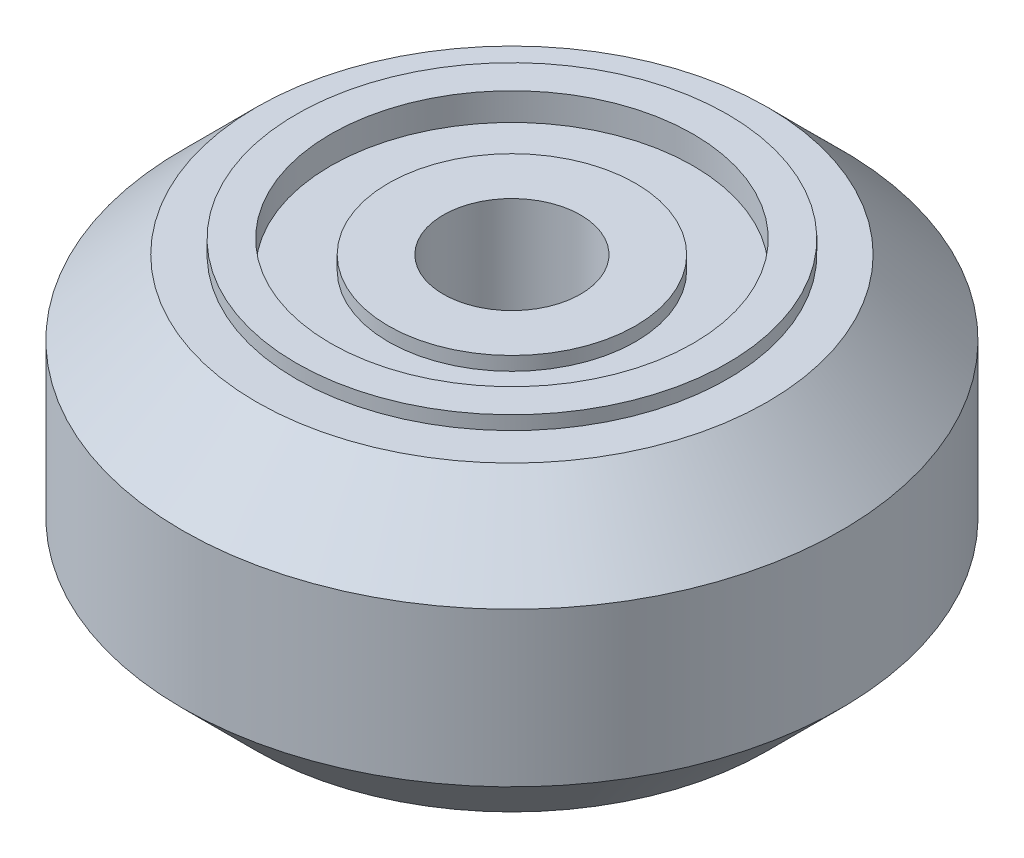
SolidWorks part; units mm, degrees
ref_plane "Alzado" through (0, 0, 0) normal (0, 0, 1) x (1, 0, 0)
ref_plane "Planta" through (0, 0, 0) normal (0, 1, 0) x (1, 0, 0)
ref_plane "Vista lateral" through (0, 0, 0) normal (1, 0, 0) x (0, 0, -1)
sketch "Sketch1" plane through (0, 0, 0) normal (0, 1, 0) x (1, 0, 0)
  circle A0 centre (0, 0) radius 12
extrude "Boss-Extrude1" add sketch "Sketch1" along normal blind 11
chamfer "Chamfer1" distance 2.7 angle 45 2 edges at (0, 0, 12) (0, 11, 12)
sketch "Sketch2" plane through (0, 0, 0) normal (0, -1, 0) x (1, 0, 0)
  circle A0 centre (0, 0) radius 2.5
extrude "Cut-Extrude1" cut sketch "Sketch2" against normal through all contours A0
sketch "Sketch3" plane through (0, 0, 0) normal (0, -1, 0) x (1, 0, 0)
  circle A0 centre (0, 0) radius 7.85
  circle A1 centre (0, 0) radius 6.6
  circle A2 centre (0, 0) radius 4.5
extrude "Boss-Extrude4" add sketch "Sketch3" along normal blind 0.5 and the other way blind 11.5 contours A0 A1 region at (-7.628, 0, 0)
extrude "Cut-Extrude2" cut sketch "Sketch3<4>" against normal blind 0.5 contours A1 A2 region at (-6.4133, 0, 0)
sketch "Sketch3<4>" plane through (0, 0, 0) normal (0, -1, 0) x (1, 0, 0) same geometry as "Sketch3"
extrude "Cut-Extrude3" cut sketch "Sketch3<5>" against normal blind 0.5 from offset 10.5 contours A1 A2 region at (-6.4133, 0, 0) offset against normal yes
sketch "Sketch3<5>" plane through (0, 0, 0) normal (0, -1, 0) x (1, 0, 0) same geometry as "Sketch3"
